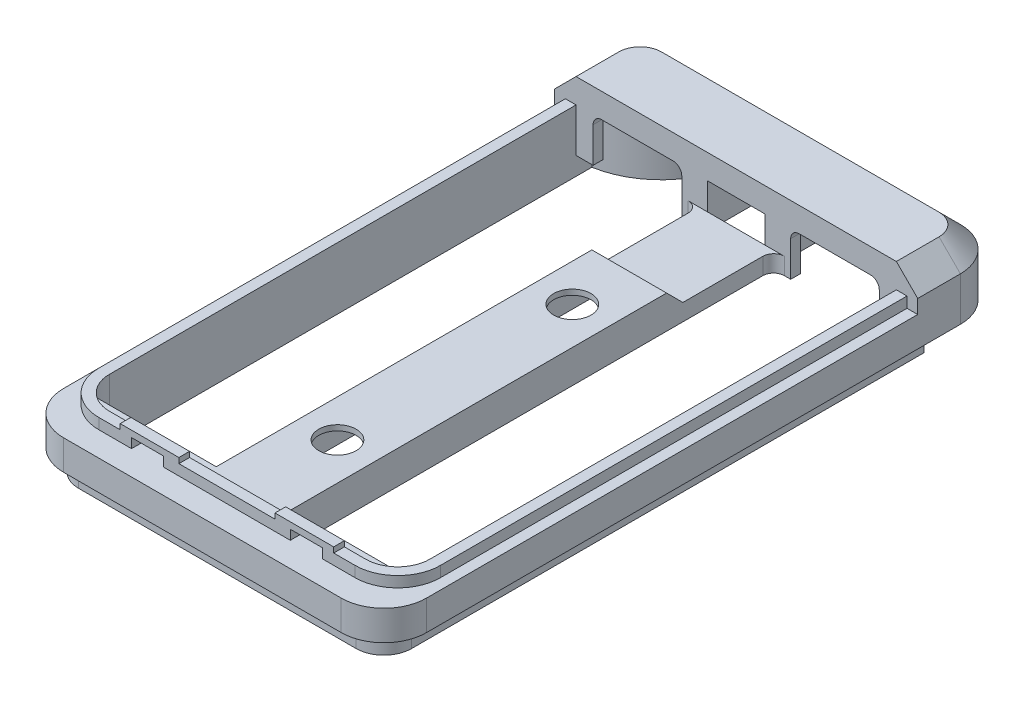
SolidWorks part; units mm, degrees
ref_plane "Front Plane" through (0, 0, 0) normal (0, 0, 1) x (1, 0, 0)
ref_plane "Top Plane" through (0, 0, 0) normal (0, 1, 0) x (1, 0, 0)
ref_plane "Right Plane" through (0, 0, 0) normal (1, 0, 0) x (0, 0, -1)
sketch "Sketch1" plane through (0, 0, 0) normal (0, 1, 0) x (1, 0, 0)
  line L0 (0, 64.3757) -> (0, -60.4293) construction
  line L1 (-70.0486, 0) -> (73.9951, 0) construction
  line L2 (-11, 27) -> (11, 27)
  line L3 (-13, 29) -> (13, 29)
  line L4 (-17, 25) -> (-17, -25)
  line L5 (-13, -29) -> (13, -29)
  line L6 (17, 25) -> (17, -25)
  line L7 (15, 23) -> (15, -23)
  line L8 (-11, -27) -> (11, -27)
  line L9 (-15, 23) -> (-15, -23)
  line L10 (17, 29) -> (17, -29) construction
  line L11 (-17, 29) -> (17, 29) construction
  line L12 (-15, 27) -> (-15, -27) construction
  line L13 (-15, -27) -> (15, -27) construction
  line L14 (-17, 29) -> (-17, -29) construction
  line L15 (-17, -29) -> (17, -29) construction
  line L16 (15, 27) -> (15, -27) construction
  line L17 (-15, 27) -> (15, 27) construction
  arc A0 (17, 25) -> (13, 29) centre (13, 25) ccw
  arc A1 (-15, -23) -> (-11, -27) centre (-11, -23) ccw
  arc A2 (-17, -25) -> (-13, -29) centre (-13, -25) ccw
  arc A3 (13, -29) -> (17, -25) centre (13, -25) ccw
  arc A4 (15, -23) -> (11, -27) centre (11, -23) cw
  arc A5 (15, 23) -> (11, 27) centre (11, 23) ccw
  arc A6 (-11, 27) -> (-15, 23) centre (-11, 23) ccw
  arc A7 (-17, 25) -> (-13, 29) centre (-13, 25) cw
  dimension "D6" = 4
  dimension "D1" = 17
  dimension "D2" = 17
  dimension "D3" = 29
  dimension "D4" = 29
  dimension "D5" = 2
extrude "Boss-Extrude2" add sketch "Sketch1" along normal blind 5.8
sketch "Sketch20" plane through (0, 0, 0) normal (1, 0, 0) x (0, 0, -1)
  line L1 (29, 5.8) -> (21, 5.8)
  line L2 (29, 5.8) -> (29, 8.1)
  line L3 (29, 8.1) -> (21, 8.1)
  line L4 (21, 5.8) -> (21, 8.1)
  dimension "D1" = 2.3
  dimension "D2" = 8
extrude "Boss-Extrude5" add sketch "Sketch20" along normal up to vertex (17 mm away) and the other way up to vertex (17 mm away) up to point (17, 5.8, -25) other way up to point (-17, 5.8, -25)
sketch "Sketch21" plane through (0, 8.1, 0) normal (0, 1, 0) x (1, 0, 0)
  line L10 (15, 21) -> (15, 25)
  line L11 (13, 27) -> (-13, 27)
  line L12 (-15, 25) -> (-15, 21)
  line L14 (17, 21) -> (17, 29)
  line L15 (-17, 21) -> (17, 21)
  line L16 (-17, 29) -> (-17, 21)
  line L17 (17, 29) -> (-17, 29)
  line L18 (17, 21) -> (17, 25)
  line L19 (-17, 21) -> (17, 21)
  line L20 (-17, 25) -> (-17, 21)
  line L21 (13, 29) -> (-13, 29)
  arc A0 (-17, 25) -> (-13, 29) centre (-13, 25) cw
  arc A1 (17, 25) -> (13, 29) centre (13, 25) ccw
  arc A2 (15, 25) -> (13, 27) centre (13, 25) ccw
  arc A3 (-15, 25) -> (-13, 27) centre (-13, 25) cw
  dimension "D2" = 4
  dimension "D1" = 0
  dimension "D3" = 2
sketch "Sketch22" plane through (0, 5.8, 0) normal (0, -1, 0) x (1, 0, 0)
  line L3 (-17, -25) -> (-17, -29)
  line L4 (-17, -25) -> (-17, -29)
  line L5 (0, -29) -> (0, 13.8194) construction
  line L6 (-13, -29) -> (-17, -29)
  line L7 (-13, -29) -> (-17, -29)
  line L8 (13, -29) -> (-13, -29) construction
  line L9 (13, -29) -> (17, -29)
  line L10 (17, -25) -> (17, -29)
  arc A2 (17, -25) -> (13, -29) centre (13, -25) cw
  arc A3 (-17, -25) -> (-13, -29) centre (-13, -25) ccw
  arc A4 (-17, -25) -> (-13, -29) centre (-13, -25) ccw
  dimension "D1" = 0
  dimension "D2" = 0
  dimension "D3" = 0
extrude "Cut-Extrude3" cut sketch "Sketch22" against normal through all
sketch "Sketch23" plane through (0, 5.8, 0) normal (0, 1, 0) x (1, 0, 0)
  line L0 (0, -29) -> (0, -24.2) construction
  line L1 (-13, -29) -> (13, -29) construction
  line L2 (-17, -24.2) -> (17, -24.2)
  line L3 (17, -25) -> (17, 21) construction
  line L16 (17, -25) -> (17, 21)
  line L17 (-13, -29) -> (13, -29)
  line L18 (-17, 21) -> (-17, -25)
  line L19 (17, -25) -> (17, -24.2)
  line L20 (-13, -29) -> (13, -29)
  line L21 (-17, -24.2) -> (-17, -25)
  arc A8 (13, -29) -> (17, -25) centre (13, -25) ccw
  arc A9 (-17, -25) -> (-13, -29) centre (-13, -25) ccw
  arc A10 (13, -29) -> (17, -25) centre (13, -25) ccw
  arc A11 (-17, -25) -> (-13, -29) centre (-13, -25) ccw
  point P10 (0, -24.2)
  dimension "D1" = 4.8
  dimension "D2" = 0
extrude "Boss-Extrude6" add sketch "Sketch23" against normal through all contours L2 L19 A10 L20 A11 L21
chamfer "Chamfer1" distance 2 angle 45 5 edges at (-17, 8.1, -23) (-15.8284, 8.1, -27.8284) (0, 8.1, -29) (15.8284, 8.1, -27.8284) (17, 8.1, -23)
sketch "Sketch25" plane through (0, 5.8, 0) normal (0, 1, 0) x (1, 0, 0)
  line L0 (4.8896, -24.2) -> (4.8896, -25.7) construction
  line L1 (-14.8158, -24.2) -> (14.8158, -24.2) construction
  line L2 (15, 21) -> (15, -22.7)
  line L3 (-15, 21) -> (-15, -22.7)
  line L4 (-12, -25.7) -> (12, -25.7)
  line L5 (-16, 21) -> (-16, -22.7)
  line L6 (-12, -26.7) -> (12, -26.7)
  line L7 (16, 21) -> (16, -22.7)
  line L8 (-16, 21) -> (-15, 21)
  line L9 (16, 21) -> (15, 21)
  arc A0 (12, -25.7) -> (15, -22.7) centre (12, -22.7) ccw
  arc A1 (-15, -22.7) -> (-12, -25.7) centre (-12, -22.7) ccw
  arc A2 (-16, -22.7) -> (-12, -26.7) centre (-12, -22.7) ccw
  arc A3 (12, -26.7) -> (16, -22.7) centre (12, -22.7) ccw
  dimension "D2" = 3
  dimension "D1" = 1.5
  dimension "D3" = 1
sketch "Sketch26" plane through (0, 5.8, 0) normal (0, 1, 0) x (1, 0, 0)
  line L9 (-17, 21) -> (-16, 21)
  line L10 (17, 21) -> (16, 21)
  line L12 (17, -25) -> (17, 21)
  line L13 (-17, 21) -> (-17, -25)
  line L14 (-13, -29) -> (13, -29)
  line L15 (17, -25) -> (17, 21)
  line L16 (13.9933, -23.2) -> (-13.9933, -23.2)
  line L17 (-14, -23) -> (-14, 22)
  line L18 (-14, 22) -> (-18, 22)
  line L19 (-18, 22) -> (-18, -25)
  line L20 (-13, -30) -> (13, -30)
  line L21 (18, -25) -> (18, 22)
  line L22 (18, 22) -> (14, 22)
  line L23 (14, 22) -> (14, -23)
  line L32 (-17, 21) -> (-17, -25)
  line L33 (-13, -29) -> (13, -29)
  line L36 (16, -22.7) -> (16, 21)
  line L37 (-12, -26.7) -> (12, -26.7)
  line L38 (-16, 21) -> (-16, -22.7)
  line L39 (16, -22.7) -> (16, 21)
  line L40 (-12, -26.7) -> (12, -26.7)
  line L41 (-16, 21) -> (-16, -22.7)
  arc A8 (-14, -23) -> (-13.9933, -23.2) centre (-11, -23) ccw
  arc A9 (-18, -25) -> (-13, -30) centre (-13, -25) ccw
  arc A10 (13, -30) -> (18, -25) centre (13, -25) ccw
  arc A11 (13.9933, -23.2) -> (14, -23) centre (11, -23) ccw
  arc A12 (-14, -23) -> (-13.9933, -23.2) centre (-11, -23) ccw
  arc A15 (13.9933, -23.2) -> (14, -23) centre (11, -23) ccw
  arc A16 (13, -29) -> (17, -25) centre (13, -25) ccw
  arc A17 (-17, -25) -> (-13, -29) centre (-13, -25) ccw
  arc A18 (13, -29) -> (17, -25) centre (13, -25) ccw
  arc A19 (-17, -25) -> (-13, -29) centre (-13, -25) ccw
  arc A20 (12, -26.7) -> (16, -22.7) centre (12, -22.7) ccw
  arc A21 (-16, -22.7) -> (-12, -26.7) centre (-12, -22.7) ccw
  arc A22 (12, -26.7) -> (16, -22.7) centre (12, -22.7) ccw
  arc A23 (-16, -22.7) -> (-12, -26.7) centre (-12, -22.7) ccw
  line M21 (-15, 21) -> (-17, 21)
  line M22 (-17, 21) -> (-17, -25)
  arc M23 (-17, -25) -> (-13, -29) centre (-13, -25) ccw
  line M24 (-13, -29) -> (13, -29)
  arc M25 (13, -29) -> (17, -25) centre (13, -25) ccw
  line M26 (17, -25) -> (17, 21)
  line M27 (17, 21) -> (15, 21)
  dimension "D1" = 1
  dimension "D2" = 0
  dimension "D3" = 0
extrude "Cut-Extrude4" cut sketch "Sketch26" against normal blind 1 contours A23 L41 L39 A22 L40 M21 M22 M23 M24 M25 M26 M27 region at (-16.5, 5.8, -20.3954)
sketch "Sketch27" plane through (0, 5.8, 0) normal (0, 1, 0) x (1, 0, 0)
  line L0 (1.9925, -26.7) -> (1.9925, -25.7) construction
  line L1 (-12, -26.7) -> (12, -26.7) construction
  line L12 (-15, -22.7) -> (15, -22.7)
  line L15 (15, -22.7) -> (15, 21)
  line L16 (-12, -25.7) -> (12, -25.7)
  line L17 (-15, 21) -> (-15, -22.7)
  line L19 (-12, -25.7) -> (12, -25.7)
  arc A8 (12, -25.7) -> (15, -22.7) centre (12, -22.7) ccw
  arc A9 (-15, -22.7) -> (-12, -25.7) centre (-12, -22.7) ccw
  arc A10 (12, -25.7) -> (15, -22.7) centre (12, -22.7) ccw
  arc A11 (-15, -22.7) -> (-12, -25.7) centre (-12, -22.7) ccw
  dimension "D1" = 1
  dimension "D2" = 1
extrude "Cut-Extrude5" cut sketch "Sketch27" against normal through all
extrude "Boss-Extrude8" add sketch "Sketch25" against normal through all
sketch "Sketch28" plane through (0, 5.8, 0) normal (0, 1, 0) x (1, 0, 0)
  line L0 (-15, -20.2999) -> (-4.5, -20.2999) construction
  line L1 (-15, 21) -> (-15, -22.7) construction
  line L2 (-4.5, -20.2999) -> (-4.5, -25.7) construction
  line L3 (-12, -25.7) -> (12, -25.7) construction
  line L4 (-12, -26.7) -> (12, -26.7) construction
  line L5 (-4.5, -25.7) -> (-10, -25.7)
  line L6 (-4.5, -25.7) -> (-4.5, -26.7)
  line L7 (-4.5, -26.7) -> (-10, -26.7)
  line L8 (-10, -25.7) -> (-10, -26.7)
  line L9 (0, -26.7) -> (0, 2.8746) construction
  line L10 (4.5, -26.7) -> (10, -26.7)
  line L11 (10, -25.7) -> (10, -26.7)
  line L12 (4.5, -25.7) -> (10, -25.7)
  line L13 (4.5, -25.7) -> (4.5, -26.7)
  dimension "D1" = 10.5
  dimension "D2" = 5.5
extrude "Boss-Extrude9" add sketch "Sketch28" along normal blind 0.5
sketch "Sketch29" plane through (0, 0, 26.7) normal (0, 0, 1) x (1, 0, 0)
  line L0 (-7.4345, 4.8) -> (-5.9345, 4.8)
  line L1 (-12, 4.8) -> (12, 4.8) construction
  line L2 (-7.4345, 4.8) -> (-8.9345, 4.8)
  line L3 (-13, 4.8) -> (13, 4.8) construction
  line L4 (-8.9345, 4.8) -> (-8.9345, 5.7)
  line L5 (-8.9345, 5.7) -> (-5.9345, 5.7)
  line L6 (-5.9345, 5.7) -> (-5.9345, 4.8)
  line L7 (0, 4.8) -> (0, 0) construction
  line L8 (8.9345, 5.7) -> (5.9345, 5.7)
  line L9 (8.9345, 4.8) -> (8.9345, 5.7)
  line L10 (7.4345, 4.8) -> (8.9345, 4.8)
  line L11 (7.4345, 4.8) -> (5.9345, 4.8)
  line L12 (5.9345, 5.7) -> (5.9345, 4.8)
  dimension "D1" = 1.5
  dimension "D2" = 1.5
  dimension "D3" = 0.9
extrude "Cut-Extrude6" cut sketch "Sketch29" against normal up to vertex (1 mm away) up to point (-4.5, 6.3, 25.7)
sketch "Sketch30" plane through (0, 4.8, 0) normal (0, 1, 0) x (1, 0, 0)
  line L0 (0, -25.7) -> (0, 21) construction
  line L1 (-4.5, -25.7) -> (4.5, -25.7) construction
  line L2 (15, 21) -> (-15, 21) construction
sketch "Sketch33" plane through (0, 0, 0) normal (0, -1, 0) x (1, 0, 0)
  line L0 (-13, -29) -> (13, -29)
  line L1 (17, -25) -> (17, 25)
  line L2 (13, 29) -> (-13, 29)
  line L3 (-17, 25) -> (-17, -25)
  line L4 (-15.6, 25) -> (-15.6, -25)
  line L5 (-13, -27.6) -> (13, -27.6)
  line L6 (15.6, -25) -> (15.6, 25)
  line L7 (13, 27.6) -> (-13, 27.6)
  arc A0 (13, -29) -> (17, -25) centre (13, -25) ccw
  arc A1 (17, 25) -> (13, 29) centre (13, 25) ccw
  arc A2 (-13, 29) -> (-17, 25) centre (-13, 25) ccw
  arc A3 (-17, -25) -> (-13, -29) centre (-13, -25) ccw
  arc A4 (-15.6, -25) -> (-13, -27.6) centre (-13, -25) ccw
  arc A5 (13, -27.6) -> (15.6, -25) centre (13, -25) ccw
  arc A6 (15.6, 25) -> (13, 27.6) centre (13, 25) ccw
  arc A7 (-13, 27.6) -> (-15.6, 25) centre (-13, 25) ccw
  dimension "D1" = 1.4
extrude "Cut-Extrude7" cut sketch "Sketch33" against normal blind 2
sketch "Sketch38" plane through (0, 0, -21) normal (0, 0, 1) x (1, 0, 0)
  line L0 (0, 8.1) -> (0, 1.1968) construction
  line L1 (15, 8.1) -> (-15, 8.1) construction
  line L2 (0, 8.1) -> (0, 5.8) construction
  line L3 (0, 5.8) -> (2.7, 5.8)
  line L5 (2.7, 5.8) -> (-2.7, 5.8)
  line L6 (2.7, 5.8) -> (2.7, 1.2858)
  line L7 (2.7, 1.2858) -> (-2.7, 1.2858)
  line L8 (-2.7, 5.8) -> (-2.7, 1.2858)
  line M12 (-15, 5.8) -> (15, 5.8)
  dimension "D1" = 2.3
  dimension "D2" = 2.7
  dimension "D3" = 5.4
sketch "Sketch39" plane through (0, 5.8, 0) normal (0, -1, 0) x (1, 0, 0)
  line L0 (-15, -21) -> (-15, -21.9)
  line L1 (-15, -21.9) -> (15, -21.9)
  line L12 (-15, -23) -> (-15, -21)
  line L13 (11, -27) -> (-11, -27)
  line L14 (15, -21) -> (15, -23)
  line L15 (-15, -23) -> (-15, -21)
  line L16 (11, -27) -> (-11, -27)
  line L17 (15, -21) -> (15, -23)
  arc A8 (-15, -23) -> (-11, -27) centre (-11, -23) ccw
  arc A9 (11, -27) -> (15, -23) centre (11, -23) ccw
  arc A10 (-15, -23) -> (-11, -27) centre (-11, -23) ccw
  arc A11 (11, -27) -> (15, -23) centre (11, -23) ccw
  line M7 (-15, -21) -> (-15, -23)
  arc M8 (-15, -23) -> (-11, -27) centre (-11, -23) ccw
  line M9 (-11, -27) -> (11, -27)
  arc M10 (11, -27) -> (15, -23) centre (11, -23) ccw
  line M11 (15, -23) -> (15, -21)
  dimension "D2" = 0.9
  dimension "D1" = 0
sketch "Sketch45" plane through (0, 0, 27.6) normal (0, 0, 1) x (1, 0, 0)
  line L3 (-5.9345, 4.8) -> (-5.9345, 5.7) construction
  line L43 (-13, 3.4) -> (13, 3.4) construction
  line L44 (-8.9345, 4.8) -> (-5.9345, 4.8) construction
  line L45 (-8.9345, 4.8) -> (-8.9345, 5.7) construction
  line L46 (-8.9345, 5.7) -> (-5.9345, 5.7) construction
  line L47 (-5.9345, 4.8) -> (-5.9345, 5.7) construction
  line L48 (5.9345, 4.8) -> (8.9345, 4.8) construction
  line L49 (5.9345, 4.8) -> (5.9345, 5.7) construction
  line L50 (5.9345, 5.7) -> (8.9345, 5.7) construction
  line L51 (8.9345, 4.8) -> (8.9345, 5.7) construction
  line L52 (-13, 4.8) -> (-13, 2) construction
  line L53 (13, 4.8) -> (13, 2) construction
  line L54 (5.9345, 1.1) -> (8.9345, 1.1)
  line L55 (8.9345, 2) -> (8.9345, 1.1)
  line L56 (5.9345, 2) -> (8.9345, 2)
  line L57 (5.9345, 2) -> (5.9345, 1.1)
  line L58 (-8.9345, 1.1) -> (-5.9345, 1.1)
  line L59 (-5.9345, 2) -> (-5.9345, 1.1)
  line L60 (-8.9345, 2) -> (-5.9345, 2)
  line L61 (-8.9345, 2) -> (-8.9345, 1.1)
extrude "Cut-Extrude14" cut sketch "Sketch45" against normal up to vertex (1.9 mm away) up to point (5.9345, 4.8, 25.7)
extrude "Cut-Extrude11" cut sketch "Sketch39" against normal blind 0.9 contours L1 M7 M8 M9 M10 M11 region at (0, 5.8, -24.3722)
sketch "Sketch40" plane through (0, 5.8, 0) normal (0, -1, 0) x (1, 0, 0)
  line L1 (-15, -21) -> (15, -21)
  line L2 (-15, -21) -> (-15, -21.9)
  line L3 (-15, -21.9) -> (15, -21.9)
  line L4 (15, -21) -> (15, -21.9)
extrude "Boss-Extrude11" add sketch "Sketch40" along normal blind 4.1
extrude "Cut-Extrude12" cut sketch "Sketch38" against normal up to next contours L8 L7 L6 M12 region at (0, 3.5429, -21)
sketch "Sketch41" plane through (0, 0, -21) normal (0, 0, 1) x (1, 0, 0)
  line L0 (2.7, 5.8) -> (5.1, 5.8) construction
  line L1 (5.9, 5.8) -> (12.6, 5.8)
  line L2 (13.4, 5) -> (13.4, 1.7)
  line L3 (15, 1.7) -> (2.7, 1.7) construction
  line L4 (5.1, 5) -> (5.1, 1.7)
  line L5 (5.1, 1.7) -> (13.4, 1.7)
  line L6 (0, 8.1) -> (0, 1.469) construction
  line L7 (15, 8.1) -> (-15, 8.1) construction
  line L8 (-5.1, 5) -> (-5.1, 1.7)
  line L9 (-5.9, 5.8) -> (-12.6, 5.8)
  line L10 (-13.4, 5) -> (-13.4, 1.7)
  line L11 (-5.1, 1.7) -> (-13.4, 1.7)
  arc A0 (13.4, 5) -> (12.6, 5.8) centre (12.6, 5) ccw
  arc A1 (5.1, 5) -> (5.9, 5.8) centre (5.9, 5) cw
  arc A2 (-5.1, 5) -> (-5.9, 5.8) centre (-5.9, 5) ccw
  arc A3 (-13.4, 5) -> (-12.6, 5.8) centre (-12.6, 5) cw
  point P10 (13.4, 5.8)
  dimension "D3" = 0.8
  dimension "D1" = 2.4
  dimension "D2" = 8.3
extrude "Cut-Extrude13" cut sketch "Sketch41" against normal up to next
sketch "Sketch43" plane through (0, 0, -21) normal (0, 0, 1) x (1, 0, 0)
  line L25 (15, 8.1) -> (-15, 8.1) construction
  line L26 (0, 8.1) -> (0, 3.3) construction
  line L28 (-2.7, 1.7) -> (-3.5, 1.7)
  line L29 (-2.7, 1.7) -> (-2.7, 3.2754)
  line L30 (-2.7, 3.2754) -> (-3.5, 3.2754)
  line L31 (-3.5, 1.7) -> (-3.5, 3.2754)
  line L32 (2.7, 1.7) -> (3.5, 1.7)
  line L33 (2.7, 1.7) -> (2.7, 3.2754)
  line L34 (2.7, 3.2754) -> (3.5, 3.2754)
  line L35 (3.5, 1.7) -> (3.5, 3.2754)
  line L36 (-3.5, 3.2754) -> (3.5, 3.2754)
  line L37 (-3.5, 3.2754) -> (-3.5, 2.7754)
  line L38 (-3.5, 2.7754) -> (3.5, 2.7754)
  line L39 (3.5, 3.2754) -> (3.5, 2.7754)
  line M6 (2.7, 1.7) -> (5.1, 1.7)
  line M32 (-5.1, 1.7) -> (-2.7, 1.7)
  line M33 (-2.7, 1.7) -> (-2.7, 5.8)
  line M35 (2.7, 5.8) -> (2.7, 1.7)
  dimension "D1" = 4.8
  dimension "D2" = 0.8
  dimension "D3" = 0.8
  dimension "D4" = 0.5
sketch "Sketch47" plane through (0, 0, -21.9) normal (0, 0, -1) x (-1, 0, 0)
  line L0 (15, 6.7) -> (-15, 6.7) construction
  line L1 (2.7, 1.7) -> (3.3, 1.7)
  line L2 (2.7, 1.7) -> (2.7, 6.7)
  line L3 (2.7, 6.7) -> (3.3, 6.7)
  line L4 (3.3, 1.7) -> (3.3, 6.7)
  line L5 (0, 6.7) -> (0, -2.5301) construction
  line L6 (-2.7, 6.7) -> (-3.3, 6.7)
  line L7 (-3.3, 1.7) -> (-3.3, 6.7)
  line L8 (-2.7, 1.7) -> (-3.3, 1.7)
  line L9 (-2.7, 1.7) -> (-2.7, 6.7)
  dimension "D1" = 0.6
extrude "Boss-Extrude13" add sketch "Sketch47" along normal up to vertex (5.1 mm away) up to point (-11, 6.7, -27)
sketch "Sketch50" plane through (0, 0, 0) normal (0, -1, 0) x (1, 0, 0)
  line L0 (-10.6681, -29) -> (-10.6681, -19) construction
  line L1 (-13, -29) -> (13, -29) construction
  line L2 (-10.6681, -19) -> (-15.6, -19) construction
  line L3 (-15.6, 25) -> (-15.6, -25) construction
  line L4 (-15.6, -23) -> (-15.6, -25)
  line L5 (-15.6, 25) -> (-15.6, -25) construction
  line L6 (-17, -15.5033) -> (-9.5, -15.5033) construction
  line L7 (-17, 25) -> (-17, -25) construction
  line L8 (-9.5, -15.5033) -> (-9.5, -27.6) construction
  line L9 (-13, -27.6) -> (13, -27.6) construction
  line L10 (-15.6, -23) -> (-9.5, -27.6) construction
  line L11 (-11.8877, -24.4217) -> (-13.2123, -26.1783) construction
  line L12 (0, -29) -> (0, -20.1634) construction
  line L13 (-15.6, -23) -> (-15.6, -22.4)
  line L14 (-9.5, -27.6) -> (-8.9, -27.6)
  line L15 (-11.8877, -24.4217) -> (-11.5264, -23.9427)
  line L16 (-13, -27.6) -> (-9.5, -27.6)
  line L17 (-13, -27.6) -> (-9.5, -27.6)
  line L18 (-13, -27.6) -> (13, -27.6)
  line L19 (-15.6, 25) -> (-15.6, -25)
  line L20 (15.6, -23) -> (15.6, -22.4)
  line L21 (9.5, -27.6) -> (8.9, -27.6)
  line L22 (15.6, -23) -> (15.6, -25)
  line L23 (13, -27.6) -> (9.5, -27.6)
  arc A0 (-9.5, -27.6) -> (-15.6, -23) centre (-8.8885, -20.4445) cw
  arc A1 (-9.5, -27.6) -> (-15.6, -23) centre (-16.2115, -30.1555) ccw
  arc A2 (9.5, -27.6) -> (15.6, -23) centre (8.8885, -20.4445) ccw
  arc A3 (9.5, -27.6) -> (15.6, -23) centre (16.2115, -30.1555) cw
  arc A4 (-15.6, -22.4) -> (-8.9, -27.6) centre (-16.3743, -30.3139) cw
  arc A5 (15.6, -22.4) -> (8.9, -27.6) centre (16.3743, -30.3139) ccw
  arc A6 (15.6, -25) -> (13, -27.6) centre (13, -25) cw
  arc A7 (-15.6, -25) -> (-13, -27.6) centre (-13, -25) ccw
  arc A8 (-15.6, -25) -> (-13, -27.6) centre (-13, -25) ccw
  arc A9 (-13.9544, -27.4185) -> (-13, -27.6) centre (-13, -25) ccw
  arc A10 (-15.6, -25) -> (-13, -27.6) centre (-13, -25) ccw
  arc A11 (13.9544, -27.4185) -> (13, -27.6) centre (13, -25) cw
  point P20 (-12.55, -25.3)
  line M6 (15, 22.7) -> (15, -23)
  arc M7 (15, -23) -> (11, -27) centre (11, -23) cw
  line M8 (11, -27) -> (-11, -27)
  arc M9 (-11, -27) -> (-15, -23) centre (-11, -23) cw
  line M10 (-15, -23) -> (-15, 22.7)
  line M15 (-15.6, 25) -> (-15.6, -25)
  arc M16 (-15.6, -25) -> (-13, -27.6) centre (-13, -25) ccw
  line M17 (-13, -27.6) -> (13, -27.6)
  arc M18 (13, -27.6) -> (15.6, -25) centre (13, -25) ccw
  line M19 (15.6, -25) -> (15.6, 25)
  dimension "D1" = 10
  dimension "D2" = 4
  dimension "D3" = 7.5
  dimension "D4" = 2.2
  dimension "D6" = 0.6
  dimension "D7" = 0.6
  dimension "D8" = 180
  dimension "D9" = 0
  dimension "D5" = 0
extrude "Boss-Extrude14" add sketch "Sketch50" against normal up to vertex (5.8 mm away) contours A4 A1 M10 M9 M8 | A4 A1 M15 M9 M10 | A4 A1 M8 M17 | A4 L15 A1 M8 | A5 A3 M6 M8 M7 | A5 A3 M8 M17 | A5 A3 M19 M6 M7 region at (-15.3004, 0, -22.7356) region at (-13.3234, 0, -23.3479) region at (-10.4663, 0, -25.5121) region at (-9.322, 0, -27.2988) region at (9.322, 0, -27.2988) region at (11.561, 0, -24.0776) region at (15.3004, 0, -22.7356) up to point (-5.9, 5.8, -21.9)
extrude "Cut-Extrude23" cut sketch "Sketch50<6>" against normal up to surface (6.7 mm away) contours A0 M17 M9 M15 M16 | A1 A0 M8 M9 | A0 A1 M8 M9 | A1 A0 M9 | A0 M9 | A2 A6 M17 M18 M19 M7 | A3 A2 M7 M8 | A3 A2 M8 M7 | A3 A2 M7 | A2 M7 region at (-13.8976, 0, -26.2161) region at (-15.1181, 0, -23.6356) region at (-12.5879, 0, -25.2283) region at (-13.4767, 0, -25.9975) region at (-10.4848, 0, -27.2157) region at (10.4848, 0, -27.2157) region at (12.5879, 0, -25.2283) region at (13.8976, 0, -26.2161) region at (15.1181, 0, -23.6356) region at (13.4767, 0, -25.9975) up to face at (-9.6857, 6.7, -24.3257)
sketch "Sketch50<6>" plane through (0, 0, 0) normal (0, -1, 0) x (1, 0, 0) same geometry as "Sketch50"
sketch "Sketch51" plane through (0, 4.8, 0) normal (0, 1, 0) x (1, 0, 0)
  line L0 (0, -29) -> (0, -24.2) construction
  line L1 (-13, -29) -> (13, -29) construction
  line L2 (0, -24.2) -> (-14.5981, -24.2)
  line L3 (0, -24.2) -> (14.5981, -24.2)
  line L34 (10, -25.7) -> (12, -25.7)
  line L35 (4.5, -25.7) -> (10, -25.7)
  line L36 (-4.5, -25.7) -> (4.5, -25.7)
  line L37 (-10, -25.7) -> (-4.5, -25.7)
  line L38 (-12, -25.7) -> (-10, -25.7)
  line L39 (10, -25.7) -> (12, -25.7)
  line L40 (4.5, -25.7) -> (10, -25.7)
  line L41 (-4.5, -25.7) -> (4.5, -25.7)
  line L42 (-10, -25.7) -> (-4.5, -25.7)
  line L43 (-12, -25.7) -> (-10, -25.7)
  arc A0 (-15, -22.7) -> (-12, -25.7) centre (-12, -22.7) ccw construction
  arc A1 (12, -25.7) -> (15, -22.7) centre (12, -22.7) ccw construction
  arc A7 (-15, -22.7) -> (-12, -25.7) centre (-12, -22.7) ccw
  arc A8 (12, -25.7) -> (15, -22.7) centre (12, -22.7) ccw
  arc A9 (-14.5981, -24.2) -> (-12, -25.7) centre (-12, -22.7) ccw
  arc A10 (12, -25.7) -> (14.5981, -24.2) centre (12, -22.7) ccw
  dimension "D1" = 4.8
  dimension "D2" = 0
extrude "Boss-Extrude15" add sketch "Sketch51" against normal blind 1
extrude "Boss-Extrude17" add sketch "Sketch43" along normal up to surface (45.2 mm away) contours L29 L38 L36 M35 | L31 L38 L29 L30 | L38 L31 M32 M33 | L38 L33 L35 M6 | L38 L35 L34 M35 region at (-3.1, 2.2377, -21) region at (-3.1, 3.0254, -21) region at (0, 3.0254, -21) region at (3.1, 2.2377, -21) region at (3.1, 3.0254, -21) up to face at (0, 4.3, 24.2)
sketch "Sketch53" plane through (0, 3.2754, 0) normal (0, 1, 0) x (1, 0, 0)
  line L0 (-3.5, 21) -> (-3.5, 12.5) construction
  line L1 (-3.5, -24.2) -> (-3.5, 21) construction
  line L3 (-3.5, 12.5) -> (3.5, 12.5)
  line L4 (-3.5, 12.5) -> (-3.5, -24.2)
  line L5 (-3.5, -24.2) -> (3.5, -24.2)
  line L6 (3.5, 12.5) -> (3.5, -24.2)
  dimension "D1" = 8.5
extrude "Boss-Extrude18" add sketch "Sketch53" along normal up to vertex up to point (14.5981, 4.8, 24.2)
chamfer "Chamfer3" distance 1.52 angle 45 1 edges at (0, 4.8, -12.5)
sketch "Sketch56" plane through (0, 4.8, 0) normal (0, 1, 0) x (1, 0, 0)
  line L0 (0, 21) -> (0, 3.9) construction
  line L1 (-2.7, 21) -> (2.7, 21) construction
  line L2 (0, 3.9) -> (0, 5.65) construction
  line L3 (0, 3.9) -> (0, -18.1) construction
  line L4 (0, -18.1) -> (0, -16.35) construction
  circle A0 centre (0, 5.65) radius 1.75
  circle A1 centre (0, -16.35) radius 1.75
  dimension "D1" = 17.1
  dimension "D2" = 1.75
  dimension "D3" = 22
  dimension "D4" = 1.75
extrude "Cut-Extrude24" cut sketch "Sketch56" against normal up to vertex contours A1 | A0 region at (0, 4.8, -5.65) region at (0, 4.8, 16.35) up to point (-3.5, 1.7, -21)
fillet "Fillet1" radius 1 2 edges at (3.5, 2.4877, -21) (-3.5, 2.4877, -21)
sketch "Sketch57" plane through (0, 2.7754, 0) normal (0, -1, 0) x (1, 0, 0)
  line L0 (0, -21) -> (0, -12.5) construction
  line L1 (-2.7, -21) -> (2.7, -21) construction
  line L2 (0, -12.5) -> (0, -10.98) construction
  line L3 (2.7, 24.2) -> (2.7, -21) construction
  line L4 (2.7, -10.98) -> (-2.7, -10.98)
  line L5 (2.7, -10.98) -> (2.7, 24.2)
  line L6 (2.7, 24.2) -> (-2.7, 24.2)
  line L7 (-2.7, -10.98) -> (-2.7, 24.2)
  dimension "D1" = 8.5
  dimension "D2" = 1.52
extrude "Cut-Extrude25" cut sketch "Sketch57" against normal blind 1.52
chamfer "Chamfer4" distance 1.52 angle 45 1 edges at (0, 4.2954, -10.98)
sketch "Sketch59" plane through (0, 0, 24.2) normal (0, 0, 1) x (1, 0, 0)
  line L8 (3.5, 3.8) -> (2.7, 3.8)
  line L9 (2.7, 3.8) -> (2.7, 1.7)
  line L10 (2.7, 1.7) -> (3.5, 1.7)
  line L11 (3.5, 1.7) -> (3.5, 3.8)
  line L12 (3.5, 3.8) -> (2.7, 3.8)
  line L13 (2.7, 3.8) -> (2.7, 1.7)
  line L14 (2.7, 1.7) -> (3.5, 1.7)
  line L15 (3.5, 1.7) -> (3.5, 3.8)
  line L20 (-2.7, 1.7) -> (-2.7, 3.8)
  line L21 (-2.7, 3.8) -> (-3.5, 3.8)
  line L22 (-3.5, 3.8) -> (-3.5, 1.7)
  line L23 (-3.5, 1.7) -> (-2.7, 1.7)
  line L24 (-2.7, 1.7) -> (-2.7, 3.8)
  line L25 (-2.7, 3.8) -> (-3.5, 3.8)
  line L26 (-3.5, 3.8) -> (-3.5, 1.7)
  line L27 (-3.5, 1.7) -> (-2.7, 1.7)
  dimension "D1" = 0
  dimension "D2" = 0
extrude "Boss-Extrude21" add sketch "Sketch59" along normal up to surface (1.5 mm away) up to face at (7.4345, 1.55, 25.7)
sketch "Sketch61" plane through (0, 3.8, 0) normal (0, -1, 0) x (1, 0, 0)
  line L0 (-3.5, 24.2) -> (-14.5981, 24.2) construction
  line L1 (-7.7905, 24.8) -> (-14.1164, 24.8)
  line L2 (-7.7905, 24.8) -> (14.116, 24.8)
  line L19 (-14.5981, 24.2) -> (15.0443, 24.2)
  line L20 (-14.5981, 24.2) -> (-14.5981, 24.8)
  line L21 (-7.7905, 24.2) -> (-7.7905, 24.8) construction
  line L22 (-14.5981, 24.8) -> (15.0443, 24.8)
  line L23 (15.0443, 24.2) -> (15.0443, 24.8)
  line M11 (-3.5, 24.2) -> (-3.5, 25.7)
  arc M13 (-12, 25.7) -> (-14.5981, 24.2) centre (-12, 22.7) ccw
  line M14 (-14.5981, 24.2) -> (-3.5, 24.2)
  dimension "D1" = 0.6
extrude "Boss-Extrude23" add sketch "Sketch61" along normal up to surface (3.8 mm away) contours L21 L1 L22 M14 M13 | L21 L19 L2 M11 | L19 L23 L22 L2 M11 region at (-11.0916, 3.8, 24.4966) region at (-5.6452, 3.8, 24.5) region at (5.7721, 3.8, 24.5) up to face at (0, 0, 0.8542)
sketch "Sketch64" plane through (0, 0, 0) normal (0, -1, 0) x (1, 0, 0)
  line L0 (0, 24.8) -> (0, 24.2) construction
  line L1 (-14.1424, 24.8) -> (14.1424, 24.8) construction
  line L2 (14.5981, 24.2) -> (-14.5981, 24.2) construction
  line L3 (0, 24.8) -> (-4.8, 24.8)
  line L5 (-4.8, 24.8) -> (4.8, 24.8)
  line L6 (-4.8, 24.8) -> (-4.8, 24.2)
  line L7 (-4.8, 24.2) -> (4.8, 24.2)
  line L8 (4.8, 24.8) -> (4.8, 24.2)
  line M3 (-14.5981, 24.2) -> (14.5981, 24.2)
  line M12 (14.1424, 24.8) -> (-14.1424, 24.8)
  dimension "D1" = 4.8
  dimension "D2" = 9.6
extrude "Cut-Extrude26" cut sketch "Sketch64" against normal up to surface (1.7 mm away) contours L0 L6 M12 M3 | L0 L7 L8 M12 region at (2.4, 0, 24.5) region at (-2.4, 0, 24.5) up to face at (-14.2, 1.7, -21.45)
sketch "Sketch65" plane through (0, 0, 0) normal (0, -1, 0) x (1, 0, 0)
  line L0 (0, 29) -> (0, 26.5) construction
  line L1 (13, 29) -> (-13, 29) construction
  line L2 (-15, 22.7) -> (-15, 23.5)
  line L3 (0, 26.5) -> (-12, 26.5)
  line L4 (-15, 26.3009) -> (-15, 26.5)
  line L5 (-15, 26.5) -> (-14.7769, 26.5)
  line L6 (0, 26.5) -> (12, 26.5)
  line L7 (15, 22.7) -> (15, 23.5)
  line L8 (15, 26.5) -> (14.8683, 26.5)
  line L9 (-15, 26.5) -> (-15, 23.6639)
  line L10 (-15, 26.5) -> (-12.0039, 26.5)
  line L11 (15, 26.5) -> (11.1332, 26.5)
  line L12 (15, 26.5) -> (15, 23.9501)
  line L13 (-14.1424, 24.8) -> (-14.7037, 24.8)
  line L14 (-14.1424, 24.8) -> (14.7037, 24.8)
  arc A0 (-12, 26.5) -> (-15, 23.5) centre (-12, 23.5) ccw
  arc A1 (12, 26.5) -> (15, 23.5) centre (12, 23.5) cw
  line M22 (-4.8, 24.8) -> (-14.1424, 24.8)
  arc M23 (-14.1424, 24.8) -> (-12, 25.7) centre (-12, 22.7) cw
  line M24 (-12, 25.7) -> (12, 25.7)
  arc M25 (12, 25.7) -> (14.1424, 24.8) centre (12, 22.7) cw
  line M26 (14.1424, 24.8) -> (4.8, 24.8)
  dimension "D2" = 3
  dimension "D1" = 2.5
extrude "Cut-Extrude27" cut sketch "Sketch65" against normal up to surface (4.2954 mm away) contours A1 L6 L3 A0 L13 L14 M23 M24 M25 | L14 M22 M26 M25 M24 M23 region at (0, 0, 26.0365) region at (0, 0, 25.2407) up to face at (0, 4.2954, 7.37)
